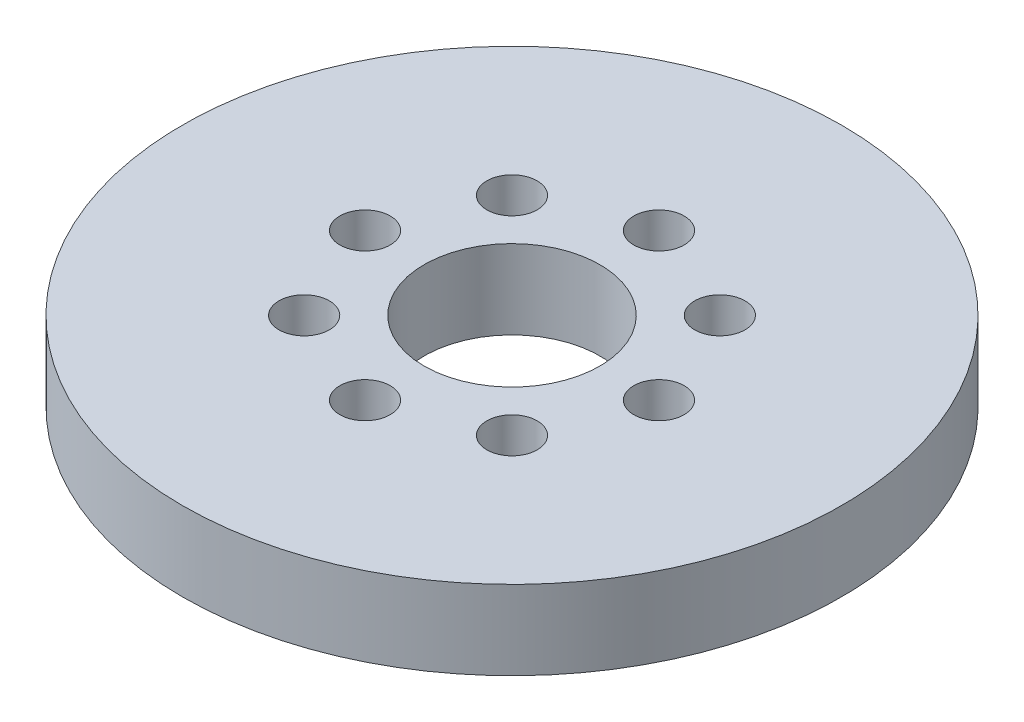
SolidWorks part; units mm, degrees
ref_plane "Front Plane" through (0, 0, 0) normal (0, 0, 1) x (1, 0, 0)
ref_plane "Top Plane" through (0, 0, 0) normal (0, 1, 0) x (1, 0, 0)
ref_plane "Right Plane" through (0, 0, 0) normal (1, 0, 0) x (0, 0, -1)
sketch "Sketch1" plane through (0, 0, 0) normal (0, 1, 0) x (1, 0, 0)
  circle A0 centre (0, 0) radius 75
  dimension "FLANGE_OD" = 150
extrude "Boss-Extrude1" add sketch "Sketch1" along normal blind 18
sketch "Sketch2" plane through (0, 0, 0) normal (0, 1, 0) x (1, 0, 0)
  circle A0 centre (0, 0) radius 20
  dimension "BORE_D" = 40
extrude "Cut-Extrude1" cut sketch "Sketch2" along normal through all
sketch "Sketch3" plane through (0, 18, 0) normal (0, 1, 0) x (1, 0, 0)
  circle A0 centre (0, 0) radius 33.4475 construction
  circle A1 centre (-33.4475, 0) radius 5.7322
  dimension "BOLT_D" = 11.4645
  dimension "BOLT_PCD" = 66.895
extrude "Cut-Extrude2" cut sketch "Sketch3" against normal blind 11.4816
pattern_circular "CirPattern1" count 8 over 360 about axis through (0, 0, 0) along (0, 1, 0) of "Cut-Extrude2"
